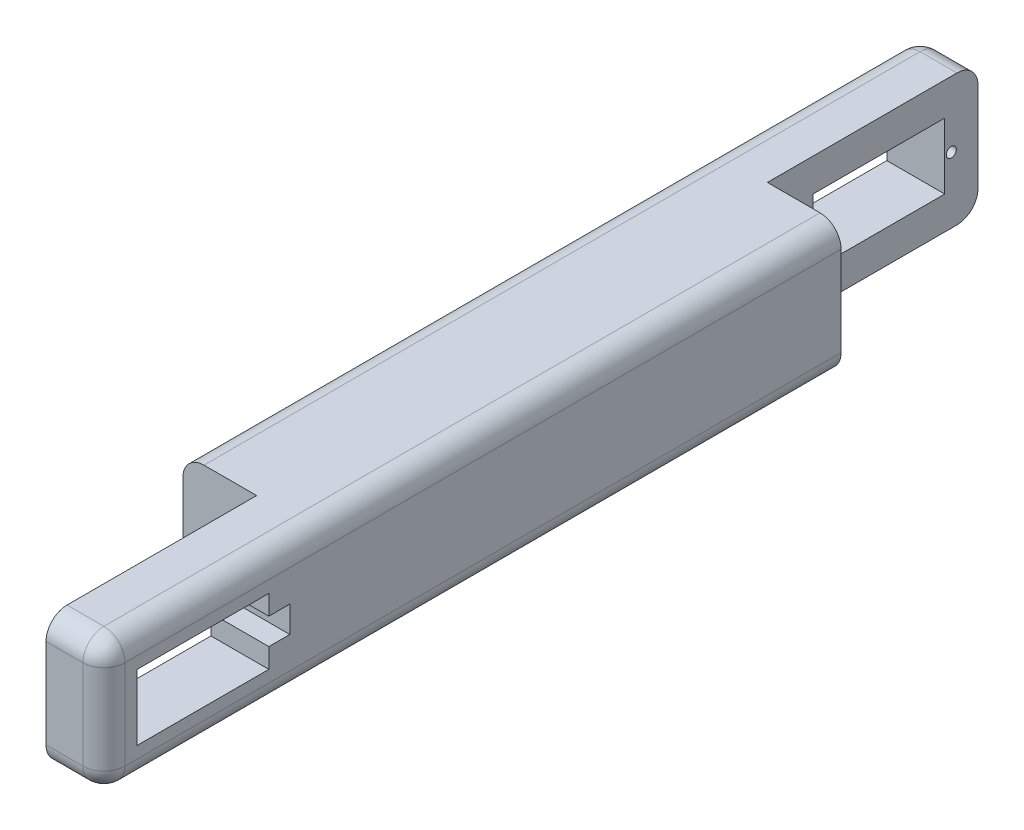
SolidWorks part; units mm, degrees
ref_plane "Front Plane" through (0, 0, 0) normal (0, 0, 1) x (1, 0, 0)
ref_plane "Top Plane" through (0, 0, 0) normal (0, 1, 0) x (1, 0, 0)
ref_plane "Right Plane" through (0, 0, 0) normal (1, 0, 0) x (0, 0, -1)
sketch "Sketch3" plane through (0, 0, 0) normal (0, 1, 0) x (1, 0, 0)
  line L1 (-12.5, 0) -> (12.5, 0)
  line L2 (-12.5, 0) -> (-12.5, 180)
  line L3 (-12.5, 180) -> (12.5, 180)
  line L4 (12.5, 0) -> (12.5, 180)
  point P4 (0, 0)
  dimension "D1" = 25
  dimension "D2" = 180
extrude "Boss-Extrude1" add sketch "Sketch3" along normal blind 25 contours L4 L3 L2 L1
sketch "Sketch4" plane through (0, 25, 0) normal (0, 1, 0) x (1, 0, 0)
  line L0 (-12.5, 0) -> (-12.5, 180) construction
  line L1 (1.5, 0) -> (-12.5, 0)
  line L2 (1.5, 0) -> (1.5, 40)
  line L3 (1.5, 40) -> (-12.5, 40)
  line L4 (-12.5, 0) -> (-12.5, 40)
  line L7 (12.5, 180) -> (-1.5, 180)
  line L8 (12.5, 180) -> (12.5, 140)
  line L9 (12.5, 140) -> (-1.5, 140)
  line L10 (-1.5, 180) -> (-1.5, 140)
  line M3 (12.5, 0) -> (12.5, 180)
  line M4 (12.5, 180) -> (-12.5, 180)
  dimension "D1" = 40
  dimension "D2" = 14
  dimension "D3" = 40
  dimension "D4" = 14
extrude "Cut-Extrude1" cut sketch "Sketch4" against normal through all contours L10 L9 M4 M3 | L3 L4 L1 L2 region at (5.5, 25, -160)
sketch "Sketch5" plane through (1.5, 0, 0) normal (-1, 0, 0) x (0, 0, 1)
  line L1 (0, 0) -> (0, 25) construction
  line L3 (0, 0) -> (-40, 0) construction
  point P0 (-25, 12.5)
  dimension "D1" = 25
  dimension "D2" = 12.5
sketch "Sketch6" plane through (1.5, 0, 0) normal (-1, 0, 0) x (0, 0, 1)
  line L0 (-32.57, 12.5) -> (-5.07, 12.5) construction
  line L1 (-18.82, 18.75) -> (-18.82, 6.25) construction
  line L2 (-31.32, 18.75) -> (-6.32, 18.75)
  line L3 (-31.32, 18.75) -> (-31.32, 6.25)
  line L4 (-31.32, 6.25) -> (-6.32, 6.25)
  line L5 (-6.32, 18.75) -> (-6.32, 6.25)
  circle A0 centre (-32.57, 12.5) radius 0.95
  circle A1 centre (-5.07, 12.5) radius 0.95
  point P0 (-32.57, 12.5)
  point P1 (-31.32, 12.5)
  point P6 (-5.07, 12.5)
  point P7 (-18.82, 12.5)
  point P9 (-18.82, 6.25)
  dimension "D5" = 1.9
  dimension "D1" = 12.5
  dimension "D2" = 25
  dimension "D3" = 6.32
  dimension "D4" = 13.75
extrude "Cut-Extrude2" cut sketch "Sketch6" against normal through all contours L5 L2 L3 L4 region at (1.5, 12.5, -18.82)
extrude "Cut-Extrude3" cut sketch "Sketch6<3>" against normal blind 9 contours A0 | A1 region at (1.5, 12.5, -32.57) region at (1.5, 12.5, -5.07)
sketch "Sketch6<3>" plane through (1.5, 0, 0) normal (-1, 0, 0) x (0, 0, 1) same geometry as "Sketch6"
sketch "Sketch8" plane through (-1.5, 0, 0) normal (1, 0, 0) x (0, 0, -1)
  line L0 (147.43, 12.5) -> (174.93, 12.5) construction
  line L1 (161.18, 18.75) -> (161.18, 6.25) construction
  line L2 (148.68, 18.75) -> (173.68, 18.75)
  line L3 (148.68, 18.75) -> (148.68, 6.25)
  line L4 (148.68, 6.25) -> (173.68, 6.25)
  line L5 (173.68, 18.75) -> (173.68, 6.25)
  line L6 (180, 0) -> (180, 25) construction
  line L7 (180, 0) -> (140, 0) construction
  circle A2 centre (147.43, 12.5) radius 0.95
  circle A3 centre (174.93, 12.5) radius 0.95
  point P0 (147.43, 12.5)
  point P1 (155, 12.5)
  point P6 (174.93, 12.5)
  point P24 (148.68, 12.5)
  point P32 (161.18, 12.5)
  dimension "D7" = 1.9
  dimension "D1" = 25
  dimension "D2" = 12.5
  dimension "D3" = 6.32
  dimension "D4" = 12.5
  dimension "D5" = 13.75
  dimension "D6" = 25
extrude "Cut-Extrude4" cut sketch "Sketch8" against normal through all contours L5 L2 L3 L4 region at (-1.5, 12.5, -161.18)
extrude "Cut-Extrude5" cut sketch "Sketch8<3>" against normal blind 9 contours A2 | A3 region at (-1.5, 12.5, -147.43)
sketch "Sketch8<3>" plane through (-1.5, 0, 0) normal (1, 0, 0) x (0, 0, -1) same geometry as "Sketch8"
fillet "Fillet1" radius 4 4 edges at (-12.5, 0, -110) (-12.5, 25, -110) (12.5, 0, -70) (12.5, 25, -70)
sketch "Sketch11" plane through (1.5, 0, 0) normal (-1, 0, 0) x (0, 0, 1)
  line L0 (-31.32, 18.75) -> (-31.32, 6.25) construction
  line L1 (-31.32, 15) -> (-35.2996, 15)
  line L2 (-31.32, 15) -> (-31.32, 10)
  line L3 (-31.32, 10) -> (-35.2996, 10)
  line L4 (-35.2996, 15) -> (-35.2996, 10)
  point P6 (-31.32, 12.5)
  point P8 (-35.2627, 10)
  point P9 (-35.041, 10)
  point P10 (-35.2996, 10)
  dimension "D1" = 5
sketch "Sketch12" plane through (-1.5, 0, 0) normal (1, 0, 0) x (0, 0, -1)
  line L0 (148.68, 15) -> (145.2134, 15)
  line L1 (148.68, 15) -> (148.68, 10)
  line L2 (148.68, 10) -> (145.2134, 10)
  line L3 (145.2134, 15) -> (145.2134, 10)
  line L4 (148.68, 18.75) -> (148.68, 6.25) construction
  point P5 (0, 0)
  point P7 (148.68, 12.5)
  point P8 (148.68, 12.5)
  point P9 (148.68, 15)
  point P10 (145.1395, 15)
  point P11 (145.2134, 15)
  dimension "D1" = 5
extrude "Cut-Extrude6" cut sketch "Sketch12" against normal blind 10 from offset 2 contours L0 L3 L2 L1 offset against normal yes
extrude "Cut-Extrude7" cut sketch "Sketch11" against normal blind 14 from offset 2 contours L4 L3 L2 L1 offset against normal yes
sketch "Sketch9" plane through (1.5, 0, 0) normal (-1, 0, 0) x (0, 0, 1)
  line L1 (-36.8183, 19.4965) -> (-3.6901, 19.4965)
  line L2 (-36.8183, 19.4965) -> (-36.8183, 4.9232)
  line L3 (-36.8183, 4.9232) -> (-3.6901, 4.9232)
  line L4 (-3.6901, 19.4965) -> (-3.6901, 4.9232)
  point P4 (-36.3248, 19.4965)
fillet "Fillet2" radius 4 5 edges at (-5, 25, -180) (-11.3284, 23.8284, -180) (-5, 0, -180) (-11.3284, 1.1716, -180) (-12.5, 12.5, -180)
fillet "Fillet3" radius 4 5 edges at (5, 25, 0) (11.3284, 23.8284, 0) (5, 0, 0) (11.3284, 1.1716, 0) (12.5, 12.5, 0)
